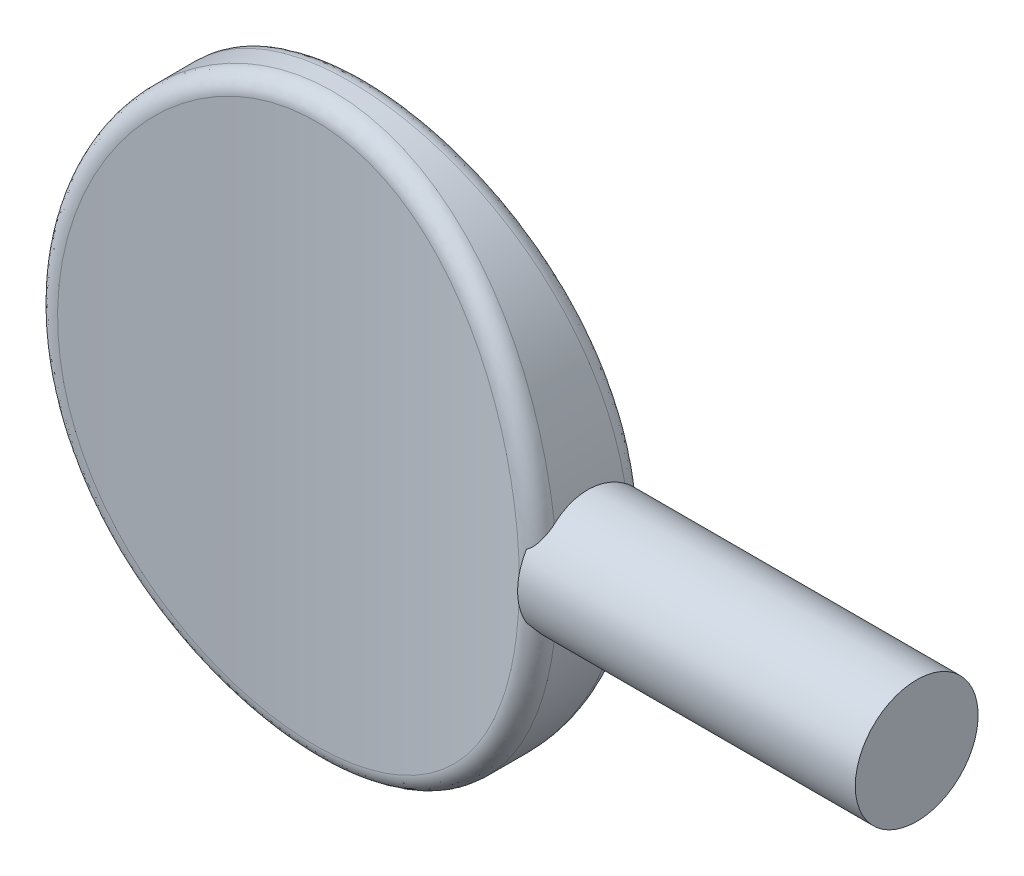
SolidWorks part; units mm, degrees
ref_plane "Front" through (0, 0, 0) normal (0, 0, 1) x (1, 0, 0)
ref_plane "Top" through (0, 0, 0) normal (0, 1, 0) x (1, 0, 0)
ref_plane "Right" through (0, 0, 0) normal (1, 0, 0) x (0, 0, -1)
ref_axis "Axis1" through (-50, 0, 0) along (1, 0, 0)
sketch "Sketch1" plane through (0, 0, 0) normal (0, 0, 1) x (1, 0, 0)
  line L0 (0, 0) -> (22.606, 0) construction
  line L1 (13.208, -2.413) -> (13.208, 2.413)
  line L2 (13.208, -2.413) -> (9.6776, -2.413) construction
  ellipse E0 centre (0, 0) end of major axis (0, -11.303) minor radius 9.906
  dimension "D2" = 3.302
  dimension "B" = 19.812
  dimension "L" = 12.7
extrude "Extrude1" add sketch "Sketch1" along normal mid plane 4.572
sketch "Sketch2" plane through (0, 0, 0) normal (0, 1, 0) x (1, 0, 0)
  line L0 (9.906, 2.286) -> (-9.906, 2.286) construction
  line L1 (0, 0) -> (0, 1.1721) construction
  line L2 (-1.7991, 0) -> (2.0444, 0) construction
  line L3 (-9.906, -2.286) -> (9.906, -2.286) construction
  line L6 (-9.906, 2.286) -> (-9.906, -2.286)
  line L7 (9.906, 2.286) -> (9.906, -2.286)
  arc A0 (-9.906, 2.286) -> (9.906, 2.286) centre (0, 40.2844) ccw
  arc A1 (-9.906, -2.286) -> (9.906, -2.286) centre (0, -40.2844) cw
extrude "Cut-Extrude1" cut sketch "Sketch2" against normal through all and the other way through all flip side to cut
fillet "Fillet3" radius 0.6773 2 edges at (-9.9037, -0.2444, 2.2854) (2.9825, 10.7785, -1.1294)
sketch "Sketch3" plane through (0, 0, 0) normal (0, 1, 0) x (1, 0, 0)
  line L1 (0, 0) -> (21.0288, 0) construction
  line L2 (0, 0) -> (22.606, 0) construction
  line L3 (13.208, 2.413) -> (13.208, 0) construction
  line L4 (13.208, 2.413) -> (22.606, 2.413)
  line L5 (22.606, 2.413) -> (22.606, 0)
  line L6 (13.208, 2.413) -> (9.3367, 2.413)
  line L7 (9.0722, 2.0783) -> (9.0722, 0)
  line L8 (9.3367, 0) -> (9.3367, 2.413) construction
  line L9 (9.0722, 0) -> (22.606, 0)
  arc A0 (9.3367, 2.413) -> (9.0722, 2.0783) centre (8.9927, 2.413) cw
  arc A3 (-9.906, 2.286) -> (9.906, 2.286) centre (0, 40.2844) ccw construction
revolve "Revolve1" add sketch "Sketch3" angle 360 about L0
cosmetic thread "Cosmetic Thread1" [suppressed]
sketch "Sketch4" plane through (0, 0, 0) normal (0, 0, 1) x (1, 0, 0)
  line L0 (0, 0) -> (27.7993, 0) construction
  line L1 (22.4227, 2.413) -> (22.606, 2.0955)
  line L2 (22.606, 2.0955) -> (22.7893, 2.413)
  line L3 (22.7893, 2.413) -> (22.7893, 2.7796)
  line L4 (22.7893, 2.7796) -> (22.4227, 2.7796)
  line L5 (22.4227, 2.7796) -> (22.4227, 2.413)
  dimension "D1" = 4.191
  dimension "D2" = 4.826
revolve "Cut-Revolve10" [suppressed] cut sketch "Sketch4" angle 360 about L0
pattern_linear "LPattern10" [suppressed] count 25 along (-1, 0, 0) of bodies 109
equation "\"D2@Sketch1\" = \"B@Sketch1\" / 6"
equation "\"D1@Fillet3\" = \"C1@Sketch2\" / 3"
equation "\"DIA@Sketch3\" = \"D@Sketch1\""
equation "\"D1@Cosmetic Thread1\" = \"L@Sketch1\""
equation "\"D1@Sketch4\" = \"D2@Cosmetic Thread1\""
equation "\"D2@Sketch4\" = \"DIA@Sketch3\""
equation "\"D1@LPattern10\" = \"D1@Cosmetic Thread1\" / \"P@LPattern10\" "
